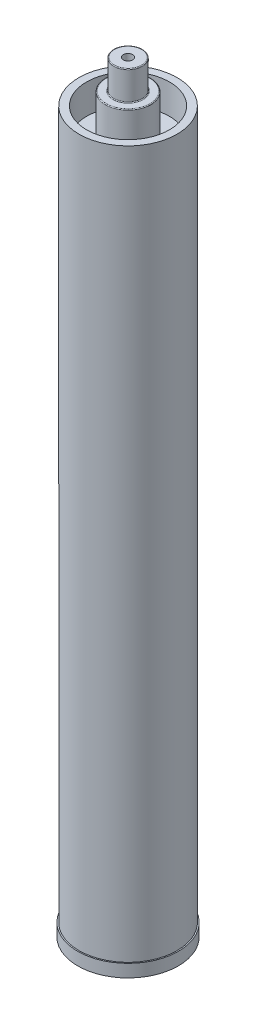
SolidWorks part; units mm, degrees
ref_plane "Front Plane" through (0, 0, 0) normal (0, 0, 1) x (1, 0, 0)
ref_plane "Top Plane" through (0, 0, 0) normal (0, 1, 0) x (1, 0, 0)
ref_plane "Right Plane" through (0, 0, 0) normal (1, 0, 0) x (0, 0, -1)
sketch "Sketch1" plane through (0, 0, 0) normal (0, 1, 0) x (1, 0, 0)
  circle A0 centre (0, 0) radius 14.351
  dimension "D1" = 28.702
extrude "Boss-Extrude1" add sketch "Sketch1" against normal blind 29.2608
sketch "Sketch2" plane through (0, -29.2608, 0) normal (0, -1, 0) x (1, 0, 0)
  circle A0 centre (0, 0) radius 22.6949
  dimension "D1" = 45.3898
extrude "Boss-Extrude2" add sketch "Sketch2" along normal blind 42.9006
sketch "Sketch3" plane through (0, -72.1614, 0) normal (0, -1, 0) x (1, 0, 0)
  circle A0 centre (0, 0) radius 49.2379
  dimension "D1" = 98.4758
extrude "Boss-Extrude3" add sketch "Sketch3" along normal blind 679.704
sketch "Sketch4" plane through (0, -72.1614, 0) normal (0, 1, 0) x (1, 0, 0)
  circle A0 centre (0, 0) radius 49.2379 construction
  circle A1 centre (0, 0) radius 49.2379
  circle A2 centre (0, 0) radius 41.6179
  dimension "D1" = 83.2358
extrude "Boss-Extrude4" add sketch "Sketch4" along normal blind 29.9212
sketch "Sketch5" plane through (0, 0, 0) normal (0, 1, 0) x (1, 0, 0)
  circle A0 centre (0, 0) radius 4.6418
  dimension "D1" = 9.2837
extrude "Cut-Extrude1" cut sketch "Sketch5" against normal blind 74.9986
sketch "Sketch6" plane through (0, -751.8654, 0) normal (0, -1, 0) x (1, 0, 0)
  circle A0 centre (0, 0) radius 50.5079
  dimension "D1" = 101.0158
extrude "Boss-Extrude5" add sketch "Sketch6" along normal blind 12.7
ref_plane "Plane1" through (0, -747.8374, 0) normal (0, -1, 0) x (-1, 0, 0)
sketch "Sketch8" plane through (0, -764.5654, 0) normal (0, -1, 0) x (1, 0, 0)
  circle A0 centre (0, 0) radius 44.6213
  dimension "D1" = 89.2426
sketch "Sketch9" plane through (0, -747.8374, 0) normal (0, -1, 0) x (-1, 0, 0)
  circle A0 centre (0, 0) radius 38.9
  dimension "D1" = 77.8
loft "Cut-Loft1" cut profiles "Sketch9", "Sketch8" connector at (0, -747.8374, -38.9) connector at (0, -764.5654, -44.6213)
fillet "Fillet1" radius 0.762 4 edges at (0, -72.1614, -22.6949) (0, -29.2608, 14.351) (0, -29.2608, -22.6949) (0, 0, 14.351)
